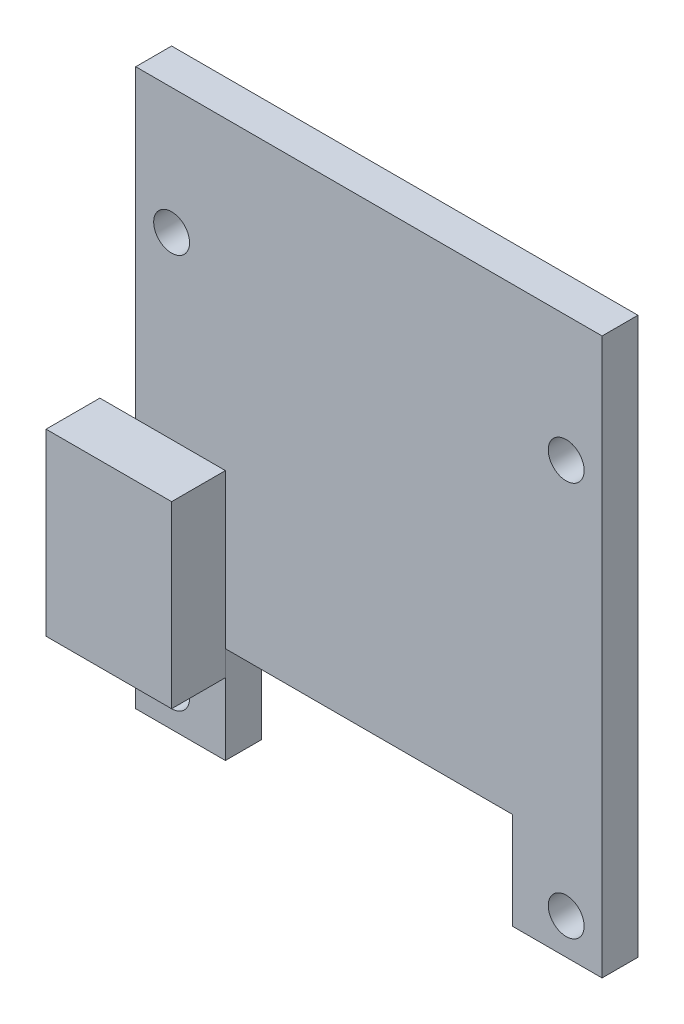
SolidWorks part; units mm, degrees
ref_plane "Front Plane" through (0, 0, 0) normal (0, 0, 1) x (1, 0, 0)
ref_plane "Top Plane" through (0, 0, 0) normal (0, 1, 0) x (1, 0, 0)
ref_plane "Right Plane" through (0, 0, 0) normal (1, 0, 0) x (0, 0, -1)
sketch "Эскиз1" plane through (0, 0, 0) normal (0, 0, 1) x (1, 0, 0)
  line L0 (-8, -15.5) -> (-8, -10.1)
  line L1 (-13, -15.5) -> (-8, -15.5)
  line L2 (-13, -15.5) -> (-13, 15.5)
  line L3 (-13, 15.5) -> (13, 15.5)
  line L4 (13, -15.5) -> (13, 15.5)
  line L5 (-13, -15.5) -> (13, 15.5) construction
  line L6 (-13, 15.5) -> (13, -15.5) construction
  line L7 (-8, -1.5) -> (-15, -1.5)
  line L8 (-8, -1.5) -> (-8, -11.5)
  line L9 (-8, -11.5) -> (-15, -11.5)
  line L10 (-15, -1.5) -> (-15, -11.5)
  line L11 (-8, -1.5) -> (-15, -11.5) construction
  line L12 (-8, -11.5) -> (-15, -1.5) construction
  line L13 (-8, -10.1) -> (8, -10.1)
  line L14 (8, -10.1) -> (8, -15.5)
  line L15 (8, -15.5) -> (13, -15.5)
  point P0 (0, 0)
  point P5 (-11.5, -6.5)
  dimension "D1" = 26
  dimension "D2" = 31
  dimension "D3" = 4
  dimension "D4" = 2
  dimension "D5" = 10
  dimension "D6" = 7
  dimension "D7" = 5
  dimension "D8" = 5
  dimension "D9" = 5.4
extrude "Бобышка-Вытянуть1" add sketch "Эскиз1" along normal blind 2 contours L14 L15 L4 L3 L2 L7 L8 L13 | L9 L0 L8 L7 L2 | L0 L9 L2 L1 region at (-10.5, -13.5, 0) region at (-10.5, -6.5, 0) region at (1.1315, 2.6184, 0)
extrude "Бобышка-Вытянуть2" add sketch "Эскиз1<3>" along normal blind 3 from surface separate body contours L7 L10 L9 L2 | L9 L0 L8 L7 L2 region at (-10.5, -6.5, 0) region at (-14, -6.5, 0) starting at face at (0, -6.4, 2)
sketch "Эскиз1<3>" plane through (0, 0, 0) normal (0, 0, 1) x (1, 0, 0) same geometry as "Эскиз1"
sketch "Эскиз2" plane through (0, 0, 2) normal (0, 0, 1) x (1, 0, 0)
  line L0 (11, 10.1828) -> (11, -14.5802) construction
  line L1 (13, -15.5) -> (13, 15.5) construction
  line L2 (8, -15.5) -> (13, -15.5) construction
  line L3 (0, 4.9723) -> (0, -5.4579) construction
  circle A0 centre (11, -13.5) radius 1
  circle A1 centre (-11, -13.5) radius 1
  circle A2 centre (11, 8.5) radius 1
  circle A3 centre (-11, 8.5) radius 1
  dimension "D1" = 2
  dimension "D4" = 22
  dimension "D2" = 2
  dimension "D3" = 2
  dimension "D5" = 22
extrude "Вырез-Вытянуть1" cut sketch "Эскиз2" against normal through all
